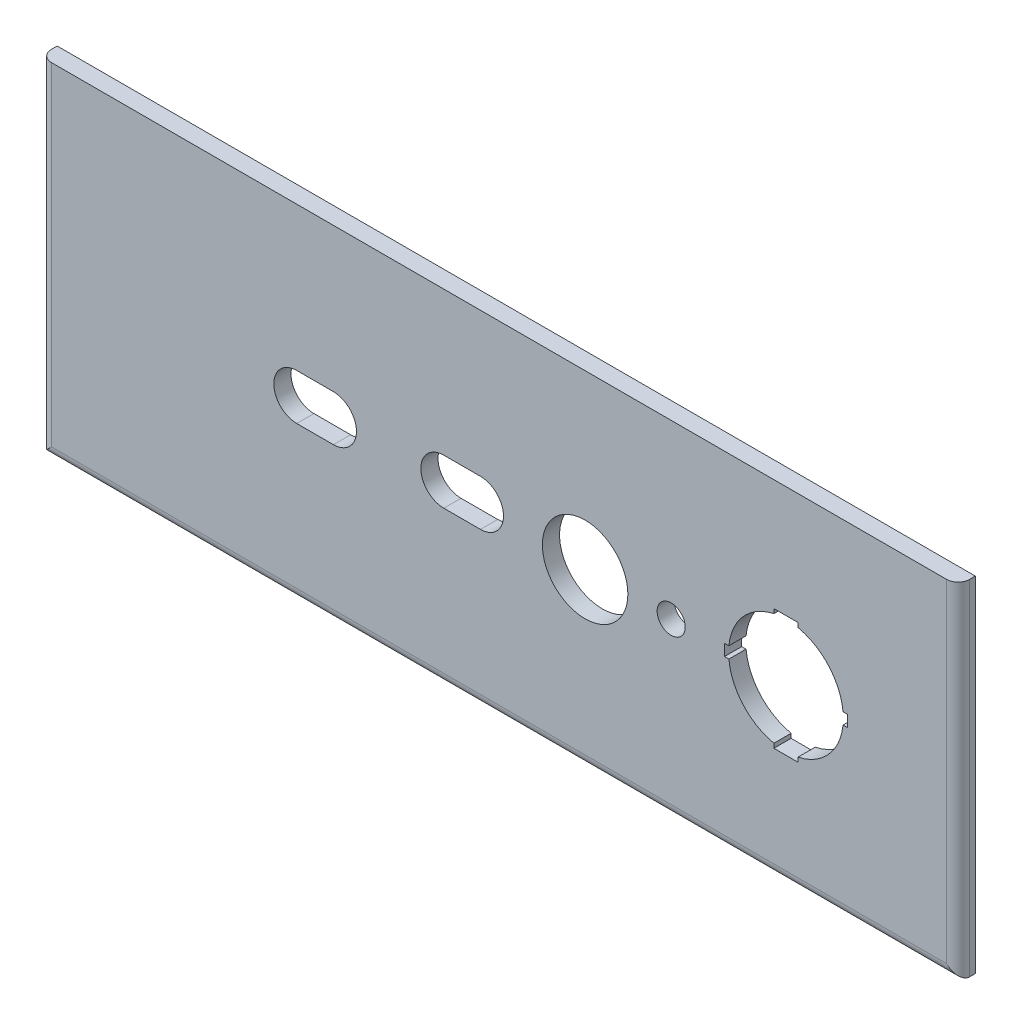
SolidWorks part; units mm, degrees
ref_plane "Front Plane" through (0, 0, 0) normal (0, 0, 1) x (1, 0, 0)
ref_plane "Top Plane" through (0, 0, 0) normal (0, 1, 0) x (1, 0, 0)
ref_plane "Right Plane" through (0, 0, 0) normal (1, 0, 0) x (0, 0, -1)
sketch "Sketch11" plane through (0, 0, 0) normal (0, 0, 1) x (1, 0, 0)
  line L0 (-39.9499, 31) -> (-40.7034, 31)
  line L1 (-40.7034, 31) -> (-40.7034, 29)
  line L2 (-40.7034, 29) -> (-39.9499, 29)
  line L3 (-30, 30) -> (-40.7034, 30) construction
  line L4 (-32.1, 20.223) -> (-32.1, 19.4571)
  line L5 (-32.1, 19.4571) -> (-27.9, 19.4571)
  line L6 (-27.9, 19.4571) -> (-27.9, 20.223)
  line L7 (-30, 30) -> (-30, 19.4571) construction
  line L8 (-27.9, 40.5429) -> (-27.9, 39.777)
  line L9 (-32.1, 40.5429) -> (-27.9, 40.5429)
  line L10 (-32.1, 39.777) -> (-32.1, 40.5429)
  line L11 (-30, 18.7333) -> (-30, 30) construction
  line L12 (-20.0501, 31) -> (-19.2966, 31)
  line L13 (-19.2966, 31) -> (-19.2966, 29)
  line L14 (-19.2966, 29) -> (-20.0501, 29)
  line L15 (-50, 30) -> (-30, 30) construction
  line L16 (-65, 30) -> (-50, 30) construction
  line L17 (0, 0) -> (-160, 0)
  line L18 (0, 0) -> (0, 60)
  line L19 (0, 60) -> (-160, 60)
  line L20 (-160, 0) -> (-160, 60)
  line L21 (-89.6273, 30.9303) -> (-83.2273, 30.9303) construction
  line L22 (-89.6273, 34.9303) -> (-83.2273, 34.9303)
  line L23 (-89.6273, 26.9303) -> (-83.2273, 26.9303)
  line L24 (-115.2528, 30.9) -> (-108.8528, 30.9) construction
  line L25 (-115.2528, 34.9) -> (-108.8528, 34.9)
  line L26 (-115.2528, 26.9) -> (-108.8528, 26.9)
  arc A0 (-39.9499, 29) -> (-32.1, 20.223) centre (-30, 30) ccw
  circle A1 centre (-30, 30) radius 10.75 construction
  arc A2 (-27.9, 20.223) -> (-20.0501, 29) centre (-30, 30) ccw
  arc A3 (-32.1, 39.777) -> (-39.9499, 31) centre (-30, 30) ccw
  arc A4 (-20.0501, 31) -> (-27.9, 39.777) centre (-30, 30) ccw
  circle A5 centre (-50, 30) radius 2.45
  circle A6 centre (-65, 30) radius 7.45
  arc A7 (-108.3028, 30.9) -> (-108.8528, 31.45) centre (-108.8528, 30.9) ccw construction
  arc A8 (-115.2528, 31.45) -> (-115.8028, 30.9) centre (-115.2528, 30.9) ccw construction
  arc A9 (-82.6773, 30.9303) -> (-83.2273, 31.4803) centre (-83.2273, 30.9303) ccw construction
  arc A10 (-89.6273, 31.4803) -> (-90.1773, 30.9303) centre (-89.6273, 30.9303) ccw construction
  arc A11 (-108.3028, 30.9) -> (-108.8528, 31.45) centre (-108.8528, 30.9) ccw construction
  arc A12 (-115.2528, 31.45) -> (-115.8028, 30.9) centre (-115.2528, 30.9) ccw construction
  arc A13 (-82.6773, 30.9303) -> (-83.2273, 31.4803) centre (-83.2273, 30.9303) ccw construction
  arc A14 (-89.6273, 31.4803) -> (-90.1773, 30.9303) centre (-89.6273, 30.9303) ccw construction
  arc A15 (-89.6273, 34.9303) -> (-89.6273, 26.9303) centre (-89.6273, 30.9303) ccw
  arc A16 (-83.2273, 26.9303) -> (-83.2273, 34.9303) centre (-83.2273, 30.9303) ccw
  arc A17 (-115.2528, 34.9) -> (-115.2528, 26.9) centre (-115.2528, 30.9) ccw
  arc A18 (-108.8528, 26.9) -> (-108.8528, 34.9) centre (-108.8528, 30.9) ccw
  point P42 (-86.4273, 30.9303)
  point P47 (-112.0528, 30.9)
  dimension "D1" = 20
  dimension "D4" = 21.5
  dimension "D5" = 4.9
  dimension "D11" = 14.9
  dimension "D2" = 2
  dimension "D3" = 4.2
  dimension "D6" = 20
  dimension "D7" = 160
  dimension "D8" = 30
  dimension "D9" = 30
  dimension "D10" = 60
  dimension "D12" = 15
  dimension "D13" = 8
extrude "Boss-Extrude1" add sketch "Sketch11" along normal blind 3 contours L20 L17 L18 L19 A5 A4 L12 L13 L14 A2 L6 L5 L4 A0 L2 L1 L0 A3 L10 L9 L8 region at (-80, 1.7088, 0)
fillet "Fillet1" radius 2 3 edges at (-80, 0, 3) (-160, 30, 3) (0, 30, 3)
